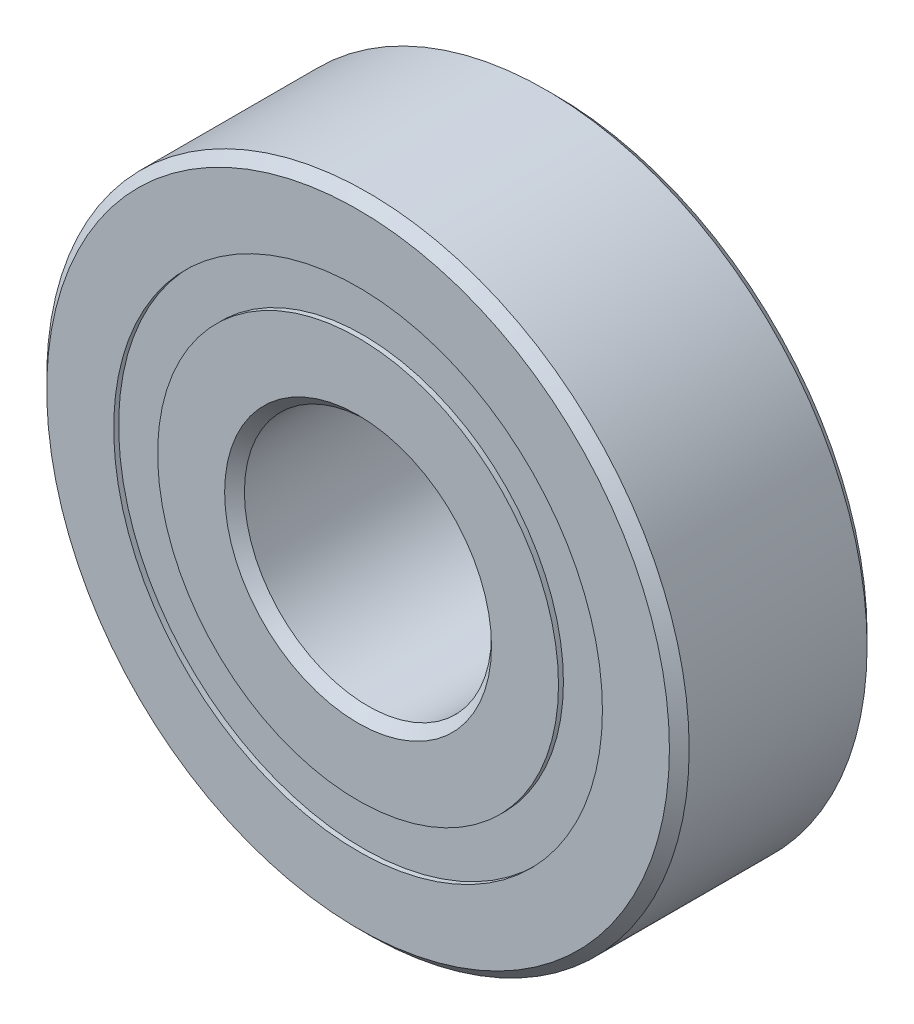
SolidWorks part; units mm, degrees
ref_plane "Front Plane" through (0, 0, 0) normal (0, 0, 1) x (1, 0, 0)
ref_plane "Top Plane" through (0, 0, 0) normal (0, 1, 0) x (1, 0, 0)
ref_plane "Right Plane" through (0, 0, 0) normal (1, 0, 0) x (0, 0, -1)
sketch "Sketch1" plane through (0, 0, 0) normal (1, 0, 0) x (0, 0, -1)
  line L0 (-2, 0) -> (2, 0) construction
  line L1 (0, 6.5) -> (0, -6.5) construction
  line L2 (1.8, 6.5) -> (-1.8, 6.5)
  line L3 (-1.8, 6.5) -> (-2, 6.3)
  line L4 (-2, 6.3) -> (-2, 4.9444)
  line L5 (-2, 4.9444) -> (-0.8889, 4.9444)
  line L6 (2, 4.9444) -> (0.8889, 4.9444)
  line L7 (2, 6.3) -> (2, 4.9444)
  line L8 (1.8, 6.5) -> (2, 6.3)
  line L9 (0, 6.5) -> (0, 4.5) construction
  line L10 (0, 4.5) -> (0, 2.5) construction
  arc A0 (-0.8889, 4.9444) -> (0.8889, 4.9444) centre (0, 4.5) cw
  arc A1 (-0.8889, 4.9444) -> (0.8889, 4.9444) centre (0, 4.5) ccw construction
  point P14 (0, 2.5)
  point P15 (0, -2.5)
  dimension "Width" = 4
  dimension "OD" = 13
  dimension "D1" = 45
  dimension "D2" = 0.2
  dimension "D3" = 1.7778
  dimension "Shaft Dia" = 5
  dimension "D4" = 0.4444
revolve "Revolve1" add sketch "Sketch1" angle 360 about L0
sketch "Sketch2" plane through (0, 0, 0) normal (1, 0, 0) x (0, 0, -1)
  line L0 (-2, 4.0556) -> (-0.8889, 4.0556)
  line L1 (-2, 6.3) -> (-2, -6.3) construction
  line L2 (-2, 4.0556) -> (-2, 2.7)
  line L3 (-2, 2.7) -> (-1.8, 2.5)
  line L4 (-1.8, 2.5) -> (1.8, 2.5)
  line L5 (0, 6.5) -> (0, -6.5) construction
  line L6 (0, 2.5) -> (0, 3.5062) construction
  line L7 (0, 3.5062) -> (0, 2.5) construction
  line L8 (-2, 4.0556) -> (-2, 1.3444) construction
  line L10 (2, 4.0556) -> (0.8889, 4.0556)
  line L11 (2, 4.0556) -> (2, 2.7)
  line L12 (2, 2.7) -> (1.8, 2.5)
  arc A0 (-0.8889, 4.0556) -> (0.8889, 4.0556) centre (0, 4.5) ccw
  arc A1 (0.8889, 4.9444) -> (-0.8889, 4.9444) centre (0, 4.5) ccw construction
  circle A2 centre (0, 4.5) radius 0.9938 construction
  dimension "D1" = 0.2
  dimension "D2" = 45
revolve "Revolve2" add sketch "Sketch2" angle 360 about L0
sketch "Sketch3" plane through (0, 0, 0) normal (1, 0, 0) x (0, 0, -1)
  line L0 (-0.9938, 4.5) -> (0.9938, 4.5)
  line L1 (0, 4.5) -> (0, 0) construction
  circle A1 centre (0, 4.5) radius 0.9938 construction
  arc A2 (-0.9938, 4.5) -> (0.9938, 4.5) centre (0, 4.5) cw
  arc A3 (0.8889, 4.9444) -> (-0.8889, 4.9444) centre (0, 4.5) ccw construction
  dimension "D1" = 1.9876
revolve "Revolve3" add sketch "Sketch3" angle 360 about L0
ref_axis "Axis1" through (0, 0, -2) along (0, 0, 1)
pattern_circular "CirPattern1" count 13 every 27.692 about axis through (0, 0, -2) along (0, 0, 1) of bodies 104
sketch "Sketch5" plane through (0, 0, 0) normal (1, 0, 0) x (0, 0, -1)
  line L0 (-2, 4.0556) -> (-0.8889, 4.0556) construction
  line L1 (-1.9, 4.9444) -> (-0.9938, 4.9444)
  line L2 (-1.9, 4.9444) -> (-1.9, 4.0556)
  line L3 (-1.9, 4.0556) -> (-0.9938, 4.0556)
  line L4 (-0.9938, 4.9444) -> (-0.9938, 4.0556)
  line L5 (0.9938, 4.9444) -> (1.9, 4.9444)
  line L6 (0.9938, 4.9444) -> (0.9938, 4.0556)
  line L7 (0.9938, 4.0556) -> (1.9, 4.0556)
  line L8 (1.9, 4.9444) -> (1.9, 4.0556)
  line L9 (-2, 4.9444) -> (-0.8889, 4.9444) construction
  line L10 (-1.9, 6.4) -> (-1.9, 4.9444) construction
  line L11 (-1.8, 6.5) -> (-2, 6.3) construction
  circle A0 centre (0, 4.5) radius 0.9938 construction
revolve "Revolve5" add sketch "Sketch5" angle 360 about L0
sketch "Sketch6" plane through (0, 0, 0) normal (0, 1, 0) x (1, 0, 0)
  point P0 (6.5, -2)
  point P1 (6.5, 2)
ref_axis "Center Axis 1" through (0, 0, -3.128) along (0, 0, 1)
ref_plane "Contact Plane 1" through (0, 0, 2) normal (0, 0, 1) x (1, 0, 0)
ref_plane "Contact Plane 2" through (0, 0, -2) normal (0, 0, -1) x (-1, 0, 0)
equation "\"D2@Sketch1\" = \"Width@Sketch1\"*.05"
equation "\"D3@Sketch1\" = \"Width@Sketch1\"/2.25"
equation "\"D4@Sketch1\" = \"D3@Sketch1\"/4"
equation "\"Balls@CirPattern1\"=\"D2@Sketch3\"*2*pi/\"D1@Sketch3\"-1"
equation "\"D2@CirPattern1\" = 360/\"Balls@CirPattern1\""
equation "\"D1@Sketch2\"=\"D2@Sketch1\""
equation "\"D1@Sketch6\"=\"Width@Sketch1\""
